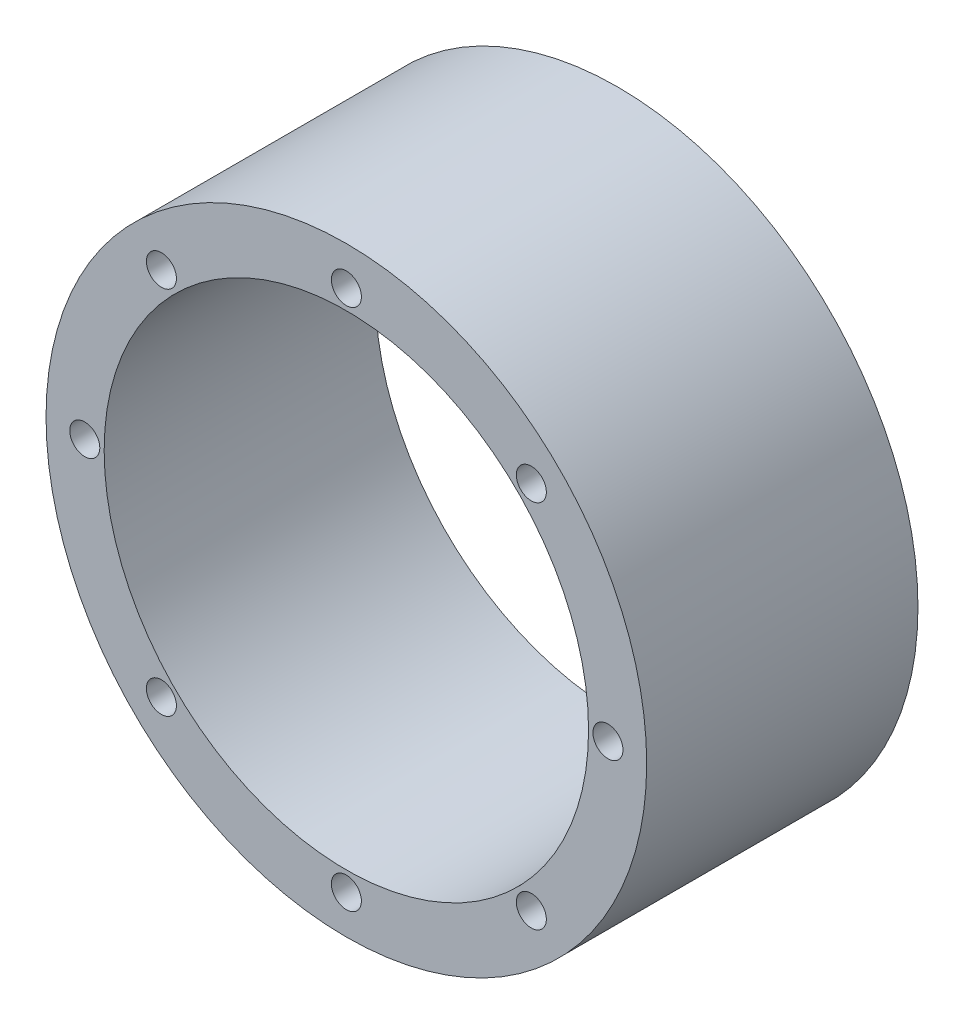
SolidWorks part; units mm, degrees
ref_plane "Front Plane" through (0, 0, 0) normal (0, 0, 1) x (1, 0, 0)
ref_plane "Top Plane" through (0, 0, 0) normal (0, 1, 0) x (1, 0, 0)
ref_plane "Right Plane" through (0, 0, 0) normal (1, 0, 0) x (0, 0, -1)
sketch "Sketch1" plane through (0, 0, 0) normal (0, 0, 1) x (1, 0, 0)
  circle A0 centre (0, 0) radius 27 construction
  circle A1 centre (-27, 0) radius 1.55
  circle A2 centre (-19.0919, 19.0919) radius 1.55
  circle A3 centre (0, 27) radius 1.55
  circle A4 centre (19.0919, 19.0919) radius 1.55
  circle A5 centre (27, 0) radius 1.55
  circle A6 centre (19.0919, -19.0919) radius 1.55
  circle A7 centre (0, -27) radius 1.55
  circle A8 centre (-19.0919, -19.0919) radius 1.55
  circle A9 centre (0, 0) radius 24 construction
  circle A10 centre (0, 0) radius 25
  circle A11 centre (0, 0) radius 31
  point P21 (0, 0)
  point P23 (0, 0)
  dimension "D1" = 8
extrude "Boss-Extrude1" add sketch "Sketch1" along normal blind 28
